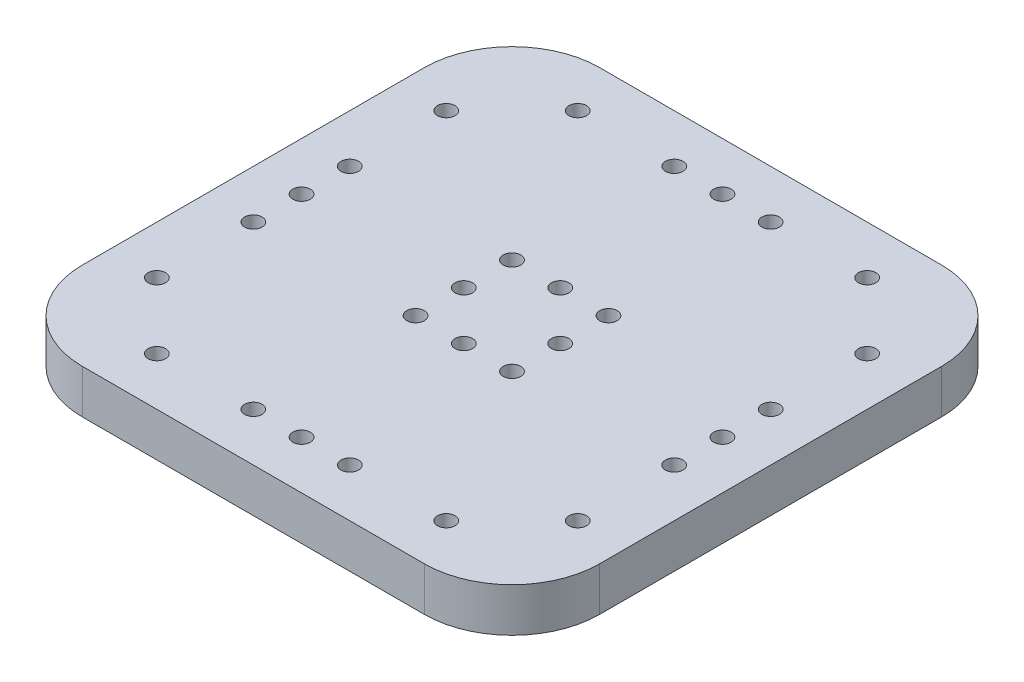
SolidWorks part; units mm, degrees
ref_plane "Front Plane" through (0, 0, 0) normal (0, 0, 1) x (1, 0, 0)
ref_plane "Top Plane" through (0, 0, 0) normal (0, 1, 0) x (1, 0, 0)
ref_plane "Right Plane" through (0, 0, 0) normal (1, 0, 0) x (0, 0, -1)
sketch "Sketch1" plane through (0, 0, 0) normal (0, 1, 0) x (1, 0, 0)
  line L0 (-1.371, 1.1217) -> (-1.371, -46.8783) construction
  line L1 (-12.371, -46.8783) -> (9.629, -46.8783) construction
  line L2 (9.629, -46.8783) -> (31.629, -46.8783) construction
  line L3 (-12.371, -46.8783) -> (-34.371, -46.8783) construction
  line L4 (-1.371, 1.1217) -> (-1.371, -9.8783) construction
  line L5 (-12.371, -9.8783) -> (9.629, -9.8783) construction
  line L6 (-1.371, 1.1217) -> (-12.371, 1.1217) construction
  line L7 (-12.371, 49.1217) -> (-34.371, 49.1217) construction
  line L8 (9.629, 49.1217) -> (31.629, 49.1217) construction
  line L9 (-12.371, 49.1217) -> (9.629, 49.1217) construction
  line L10 (-60.371, 60.1217) -> (57.629, -57.8783) construction
  line L11 (46.629, 12.1217) -> (46.629, 34.1217) construction
  line L12 (46.629, -9.8783) -> (46.629, -31.8783) construction
  line L13 (46.629, 12.1217) -> (46.629, -9.8783) construction
  line L14 (-49.371, 12.1217) -> (-49.371, -9.8783) construction
  line L15 (-49.371, -9.8783) -> (-49.371, -31.8783) construction
  line L16 (-49.371, 12.1217) -> (-49.371, 34.1217) construction
  line L18 (-60.371, 60.1217) -> (57.629, 60.1217)
  line L19 (-60.371, 60.1217) -> (-60.371, -57.8783)
  line L20 (-60.371, -57.8783) -> (57.629, -57.8783)
  line L21 (57.629, 60.1217) -> (57.629, -57.8783)
  line L22 (-60.371, 60.1217) -> (57.629, -57.8783) construction
  line L23 (-60.371, -57.8783) -> (57.629, 60.1217) construction
  circle A0 centre (-1.371, -46.8783) radius 2
  circle A1 centre (9.629, -46.8783) radius 2
  circle A2 centre (31.629, -46.8783) radius 2
  circle A3 centre (-34.371, -46.8783) radius 2
  circle A4 centre (-12.371, -46.8783) radius 2
  circle A5 centre (-1.371, -9.8783) radius 2
  circle A6 centre (9.629, -9.8783) radius 2
  circle A7 centre (-12.371, -9.8783) radius 2
  circle A8 centre (-12.371, 1.1217) radius 2
  circle A9 centre (-12.371, 12.1217) radius 2
  circle A10 centre (9.629, 12.1217) radius 2
  circle A11 centre (-1.371, 12.1217) radius 2
  circle A12 centre (-12.371, 49.1217) radius 2
  circle A13 centre (-34.371, 49.1217) radius 2
  circle A14 centre (31.629, 49.1217) radius 2
  circle A15 centre (9.629, 49.1217) radius 2
  circle A16 centre (-1.371, 49.1217) radius 2
  circle A17 centre (9.629, 1.1217) radius 2
  circle A18 centre (46.629, 12.1217) radius 2
  circle A19 centre (46.629, 34.1217) radius 2
  circle A20 centre (46.629, -31.8783) radius 2
  circle A21 centre (46.629, -9.8783) radius 2
  circle A22 centre (46.629, 1.1217) radius 2
  circle A23 centre (-49.371, 1.1217) radius 2
  circle A24 centre (-49.371, -9.8783) radius 2
  circle A25 centre (-49.371, -31.8783) radius 2
  circle A26 centre (-49.371, 34.1217) radius 2
  circle A27 centre (-49.371, 12.1217) radius 2
  dimension "D1" = 48
  dimension "D2" = 11
  dimension "D3" = 22
  dimension "D4" = 11
extrude "Boss-Extrude1" add sketch "Sketch1" along normal blind 10
fillet "Fillet1" radius 20 4 edges at (-60.371, 5, -60.1217) (57.629, 5, -60.1217) (57.629, 5, 57.8783) (-60.371, 5, 57.8783)
